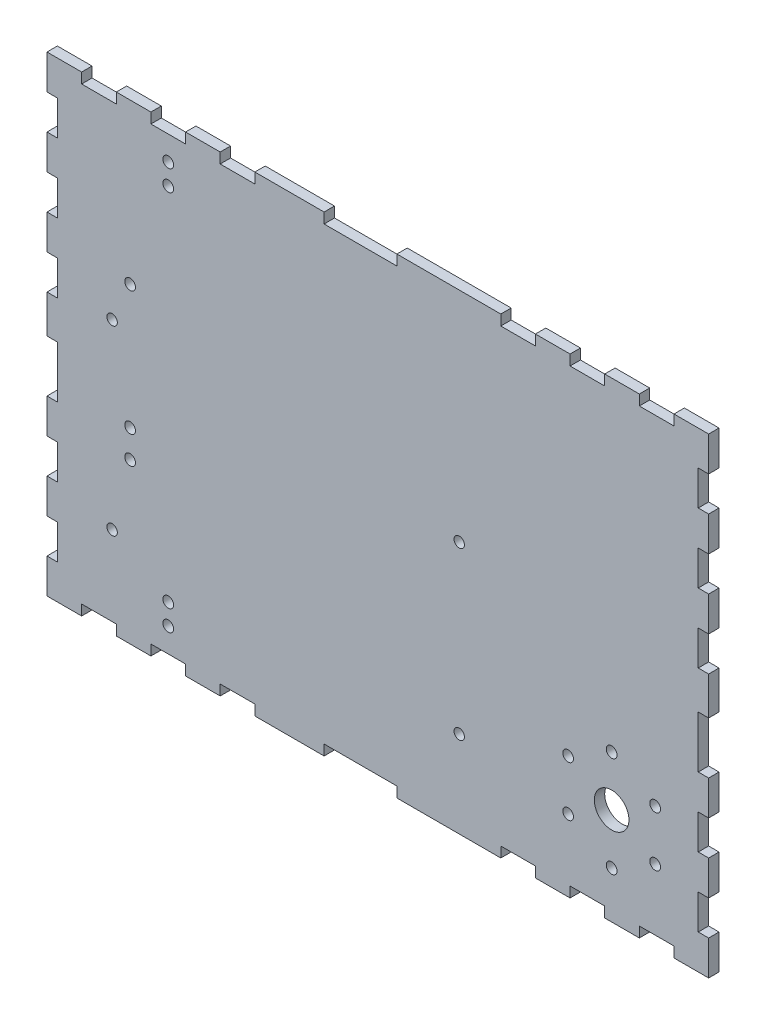
SolidWorks part; units mm, degrees
ref_plane "Front Plane" through (0, 0, 0) normal (0, 0, 1) x (1, 0, 0)
ref_plane "Top Plane" through (0, 0, 0) normal (0, 1, 0) x (1, 0, 0)
ref_plane "Right Plane" through (0, 0, 0) normal (1, 0, 0) x (0, 0, -1)
sketch "Sketch2" plane through (0, 0, 0) normal (0, 0, 1) x (1, 0, 0)
  line L1 (0, 0) -> (191, 0)
  line L2 (0, 0) -> (0, 136)
  line L3 (0, 136) -> (191, 136)
  line L4 (191, 0) -> (191, 136)
  circle A0 centre (35, 16) radius 1.55 construction
  circle A1 centre (35, 10) radius 1.55 construction
  circle A2 centre (24, 46.0692) radius 1.55 construction
  circle A3 centre (24, 54.0692) radius 1.55 construction
  circle A5 centre (24, 89.9308) radius 1.55 construction
  circle A6 centre (35, 120) radius 1.55 construction
  circle A7 centre (35, 126) radius 1.55 construction
  circle A8 centre (175.5574, 35.25) radius 1.55 construction
  circle A9 centre (163, 42.5) radius 1.55 construction
  circle A10 centre (150.4426, 35.25) radius 1.55 construction
  circle A11 centre (150.4426, 20.75) radius 1.55 construction
  circle A12 centre (163, 13.5) radius 1.55 construction
  circle A13 centre (175.5574, 20.75) radius 1.55 construction
  circle A14 centre (35, 16) radius 1.55
  circle A15 centre (35, 10) radius 1.55
  circle A16 centre (24, 46.0692) radius 1.55
  circle A17 centre (24, 54.0692) radius 1.55
  circle A18 centre (18.8, 26) radius 1.5 construction
  circle A19 centre (24, 89.9308) radius 1.55
  circle A20 centre (35, 120) radius 1.55
  circle A21 centre (35, 126) radius 1.55
  circle A22 centre (175.5574, 35.25) radius 1.55
  circle A23 centre (163, 42.5) radius 1.55
  circle A24 centre (150.4426, 35.25) radius 1.55
  circle A25 centre (150.4426, 20.75) radius 1.55
  circle A26 centre (163, 13.5) radius 1.55
  circle A27 centre (175.5574, 20.75) radius 1.55
  circle A28 centre (18.8, 78.5) radius 1.5 construction
  circle A29 centre (18.8, 78.5) radius 1.5
  circle A30 centre (119, 73) radius 1.5 construction
  circle A31 centre (119, 25) radius 1.5 construction
  circle A32 centre (18.8, 26) radius 1.5
  circle A33 centre (119, 73) radius 1.5
  circle A34 centre (119, 25) radius 1.5
extrude "Boss-Extrude1" add sketch "Sketch2" along normal blind 3
ref_axis "Axis1" through (0, 68, 3) along (1, 0, 0)
ref_plane "Plane1" through (0, 68, 0) normal (0, 1, 0) x (1, 0, 0)
ref_axis "Axis2" through (95.5, 0, 3) along (0, 1, 0)
ref_plane "Plane2" through (95.5, 0, 0) normal (1, 0, 0) x (0, 0, -1)
sketch "Sketch3" plane through (0, 0, 3) normal (0, 0, 1) x (1, 0, 0)
  line L0 (0, 3) -> (191, 3) construction
  line L1 (0, 136) -> (0, 0) construction
  line L2 (191, 0) -> (191, 136) construction
  line L3 (0, 0) -> (191, 0) construction
  line L4 (10, 0) -> (10, 3)
  line L5 (20, 0) -> (20, 3)
  line L6 (30, 0) -> (30, 3)
  line L7 (40, 0) -> (40, 3)
  line L8 (50, 0) -> (50, 3)
  line L9 (60, 0) -> (60, 3)
  line L10 (10, 0) -> (20, 0)
  line L11 (20, 3) -> (10, 3)
  line L12 (30, 0) -> (40, 0)
  line L13 (40, 3) -> (30, 3)
  line L14 (50, 0) -> (60, 0)
  line L15 (80, 3) -> (80, 0)
  line L16 (60, 3) -> (50, 3)
  line L17 (181, 0) -> (181, 3)
  line L18 (171, 0) -> (171, 3)
  line L19 (161, 0) -> (161, 3)
  line L20 (151, 0) -> (151, 3)
  line L21 (141, 0) -> (141, 3)
  line L22 (131, 0) -> (131, 3)
  line L23 (181, 0) -> (171, 0)
  line L24 (171, 0) -> (170.9794, -0.0476)
  line L25 (171, 3) -> (181, 3)
  line L26 (181, 3) -> (181.0353, 3.2173)
  line L27 (161, 0) -> (151, 0)
  line L28 (161, 3) -> (151, 3)
  line L29 (141, 0) -> (131, 0)
  line L30 (131, 3) -> (141, 3)
  line L31 (141, 3) -> (140.9859, 2.9583)
  line L32 (101, 0) -> (101, 3)
  line L33 (80, 0) -> (101, 0)
  line L34 (101, 3) -> (80, 3)
  line M15 (0, 0) -> (191, 0)
  dimension "D6" = 20
  dimension "D1" = 3
  dimension "D2" = 10
  dimension "D4" = 10
  dimension "D7" = 30
  dimension "D3" = 6
  dimension "D5" = 6
extrude "Cut-Extrude1" cut sketch "Sketch3" against normal up to next contours L5 L11 L4 M15 | L7 L13 L6 M15 | L9 L16 L8 M15 | L32 L34 L15 M15 | L30 L22 L21 M15 | L19 L28 L20 M15 | L25 L18 L17 M15 region at (176, 1.5, 3) region at (156, 1.5, 3) region at (136, 1.5, 3) region at (90.5, 1.5, 3) region at (55, 1.5, 3) region at (35, 1.5, 3) region at (15, 1.5, 3)
mirror "Mirror1" about plane through (0, 68, 0) normal (0, 1, 0) of "Cut-Extrude1"
sketch "Sketch4" plane through (0, 0, 3) normal (0, 0, 1) x (1, 0, 0)
  line L0 (3, 136) -> (3, 0) construction
  line L1 (10, 136) -> (0, 136) construction
  line L2 (0, 0) -> (10, 0) construction
  line L3 (0, 136) -> (0, 0) construction
  line L4 (0, 126) -> (3, 126)
  line L5 (0, 116) -> (3, 116)
  line L6 (0, 106) -> (3, 106)
  line L7 (0, 96) -> (3, 96)
  line L8 (0, 86) -> (3, 86)
  line L9 (0, 10) -> (3, 10)
  line L10 (0, 20) -> (3, 20)
  line L11 (0, 30) -> (3, 30)
  line L12 (0, 40) -> (3, 40)
  line L13 (0, 50) -> (3, 50)
  line L14 (0, 126) -> (0, 116)
  line L15 (3, 116) -> (3, 126)
  line L16 (0, 106) -> (0, 96)
  line L17 (3, 96) -> (3, 106)
  line L18 (0, 20) -> (0, 10)
  line L19 (3, 10) -> (3, 20)
  line L20 (0, 30) -> (0, 40)
  line L21 (3, 30) -> (3, 40)
  line L22 (0, 65) -> (3, 65)
  line L23 (0, 76) -> (3, 76)
  line L24 (0, 86) -> (0, 76)
  line L25 (3, 76) -> (3, 86)
  line L26 (0, 65) -> (0, 50)
  line L27 (3, 50) -> (3, 65)
  dimension "D1" = 3
  dimension "D2" = 10
  dimension "D4" = 10
  dimension "D6" = 15
  dimension "D3" = 6
  dimension "D5" = 5
extrude "Cut-Extrude2" cut sketch "Sketch4" against normal up to next
mirror "Mirror2" about plane through (95.5, 0, 0) normal (1, 0, 0) of "Cut-Extrude2"
sketch "Sketch6" plane through (0, 0, 3) normal (0, 0, 1) x (1, 0, 0)
  line L0 (116, 0) -> (116, 136) construction
  line L1 (101, 0) -> (131, 0) construction
  line L2 (131, 136) -> (101, 136) construction
  line L3 (191, 68) -> (85, 68) construction
  line L4 (191, 65) -> (191, 76) construction
  dimension "D1" = 106
ref_point "MountPoint-Dif"
sketch "Sketch8" plane through (0, 0, 0) normal (0, 0, -1) x (-1, 0, 0)
  circle A0 centre (-163, 28) radius 8 construction
  circle A1 centre (-163, 28) radius 8
  circle A2 centre (-163, 28) radius 5
  dimension "D1" = 10
extrude "Cut-Extrude3" cut sketch "Sketch8" against normal up to next contours A2 region at (163, 28, 0)
